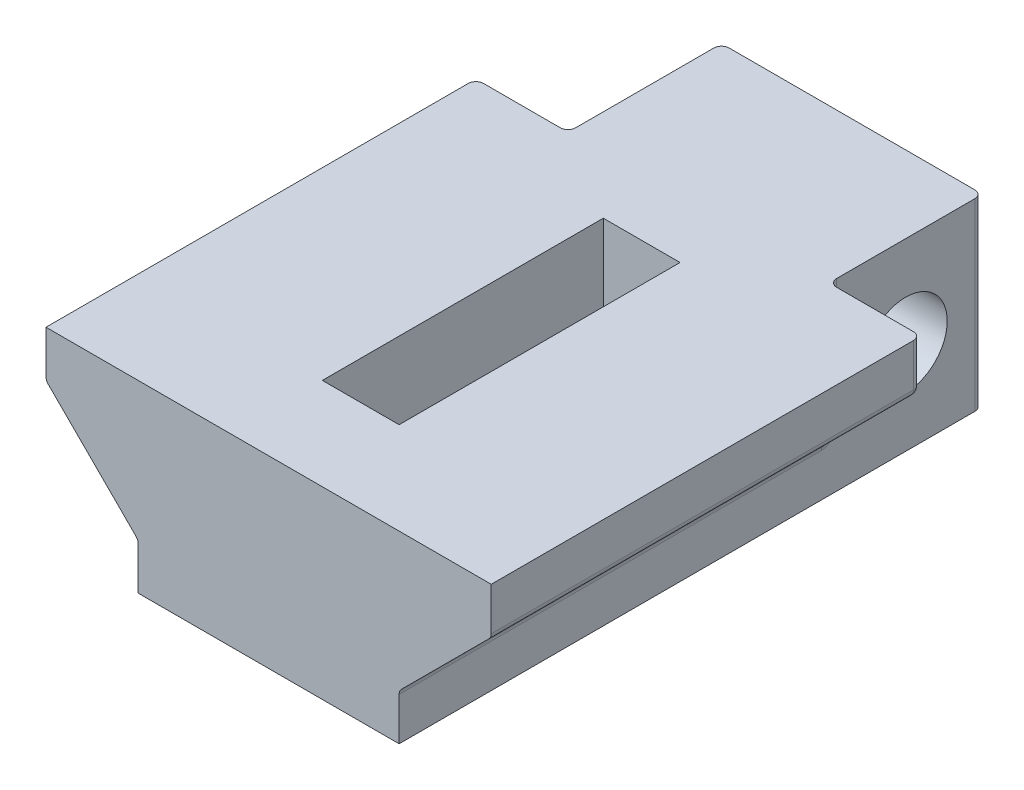
SolidWorks part; units mm, degrees
material "ABS"
ref_plane "Front Plane" through (0, 0, 0) normal (0, 0, 1) x (1, 0, 0)
ref_plane "Top Plane" through (0, 0, 0) normal (0, 1, 0) x (1, 0, 0)
ref_plane "Right Plane" through (0, 0, 0) normal (1, 0, 0) x (0, 0, -1)
sketch "Sketch1" plane through (0, 0, 0) normal (0, 0, 1) x (1, 0, 0)
  line L0 (0, 0) -> (0, 12) construction
  line L1 (-14.5, 12) -> (-14.5, 9)
  line L2 (-14.5, 9) -> (-8.5, 3)
  line L3 (-8.5, 3) -> (-8.5, 0)
  line L4 (8.5, 3) -> (8.5, 0)
  line L5 (14.5, 9) -> (8.5, 3)
  line L6 (14.5, 12) -> (14.5, 9)
  line L7 (-14.5, 12) -> (14.5, 12)
  line L8 (-8.5, 0) -> (8.5, 0)
  dimension "D1" = 12
  dimension "D2" = 3
  dimension "D3" = 45
  dimension "D4" = 17
extrude "Dovetail Body" add sketch "Sketch1" along normal mid plane 38
sketch "Sketch9" plane through (0, 0, -19) normal (0, 0, -1) x (-1, 0, 0)
  line L0 (0, 12) -> (0, 0) construction
  line L1 (-14.5, 12) -> (-8.5, 12)
  line L2 (-14.5, 12) -> (-14.5, 0)
  line L3 (-14.5, 0) -> (-8.5, 0)
  line L4 (-8.5, 12) -> (-8.5, 0)
  line L5 (-14.5, 12) -> (14.5, 12) construction
  line L6 (8.5, 0) -> (-8.5, 0) construction
  line L7 (8.5, 12) -> (8.5, 0)
  line L8 (14.5, 0) -> (8.5, 0)
  line L9 (14.5, 12) -> (14.5, 0)
  line L10 (14.5, 12) -> (8.5, 12)
extrude "Bolt Clearance" cut sketch "Sketch9" against normal blind 10
sketch "Sketch10" plane through (8.5, 0, 0) normal (1, 0, 0) x (0, 0, -1)
  line L0 (14, 12) -> (14, 0) construction
  line L1 (9, 12) -> (19, 12) construction
  line L2 (-19, 0) -> (19, 0) construction
  circle A0 centre (14, 6) radius 2.7
  dimension "D1" = 5.4
extrude "Bolt Insert" cut sketch "Sketch10" against normal through all
sketch "Sketch11" plane through (0, 0, 0) normal (0, -1, 0) x (1, 0, 0)
  line L0 (0, -5.3) -> (0, 0) construction
  line L1 (2.5, -5.3) -> (-2.5, -5.3)
  line L2 (2.5, -5.3) -> (2.5, 13)
  line L3 (2.5, 13) -> (-2.5, 13)
  line L4 (-2.5, -5.3) -> (-2.5, 13)
  line L5 (8.5, 19) -> (8.5, -19) construction
  line L6 (-8.5, 19) -> (8.5, 19) construction
  line L7 (8.5, -16.7) -> (8.5, -11.3) construction
  line L8 (8.5, -16.7) -> (8.5, -11.3) construction
  dimension "D1" = 6
  dimension "D2" = 6
  dimension "D3" = 6
extrude "Weight Clearance" cut sketch "Sketch11" against normal through all
fillet "Contouring" radius 0.5 12 edges at (8.5, 7.5, -9) (-8.5, 7.5, -9) (8.5, 3, 5) (-8.5, 3, 5) (-14.5, 9, 5) (14.5, 9, 5) (-11.5, 6, -9) (-14.5, 10.5, -9) (-8.5, 6, -19) (8.5, 6, -19) (11.5, 6, -9) (14.5, 10.5, -9)
equation "\"width keep\"= 3"
equation "\"dovetail height\"= 12"
equation "\"dovetail angle\"= 45"
equation "\"dovetail width\" = 17"
equation "\"D1@Sketch1\"=\"dovetail height\""
equation "\"D2@Sketch1\"=\"width keep\""
equation "\"D3@Sketch1\"=\"dovetail angle\""
equation "\"D4@Sketch1\"=\"dovetail width\""
equation "\"dovetail length\"= 38"
equation "\"D1@Dovetail Body\" = \"dovetail length\""
equation "\"print free\"= 0.45"
equation "\"print fit\"= 0.2"
equation "\"D1@Sketch11\"=2*\"width keep\""
equation "\"D2@Sketch11\"=\"D1@Sketch11\""
equation "\"D3@Sketch11\"=\"D2@Sketch11\""
